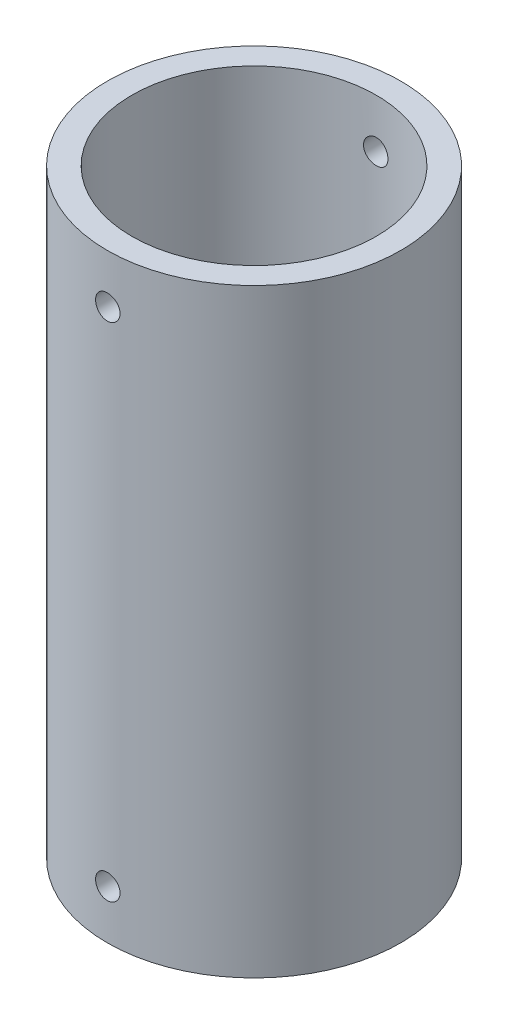
SolidWorks part; units mm, degrees
ref_plane "Front Plane" through (0, 0, 0) normal (0, 0, 1) x (1, 0, 0)
ref_plane "Top Plane" through (0, 0, 0) normal (0, 1, 0) x (1, 0, 0)
ref_plane "Right Plane" through (0, 0, 0) normal (1, 0, 0) x (0, 0, -1)
sketch "Sketch1" plane through (0, 0, 0) normal (0, 1, 0) x (1, 0, 0)
  circle A0 centre (0, 0) radius 31.75
  circle A1 centre (0, 0) radius 38.1
  dimension "D1" = 76.2
  dimension "D2" = 6.35
extrude "Boss-Extrude1" add sketch "Sketch1" along normal blind 155.702
sketch "Sketch2" plane through (0, 0, 0) normal (0, 0, 1) x (1, 0, 0)
  line L0 (-38.1, 0) -> (38.1, 0) construction
  line L1 (38.1, 155.702) -> (-38.1, 155.702) construction
  circle A0 centre (0, 143.002) radius 3.175
  circle A1 centre (0, 12.7) radius 3.175
  dimension "D3" = 6.35
  dimension "D4" = 6.35
  dimension "D1" = 12.7
  dimension "D2" = 12.7
extrude "Cut-Extrude1" cut sketch "Sketch2" against normal through all both and the other way through all
